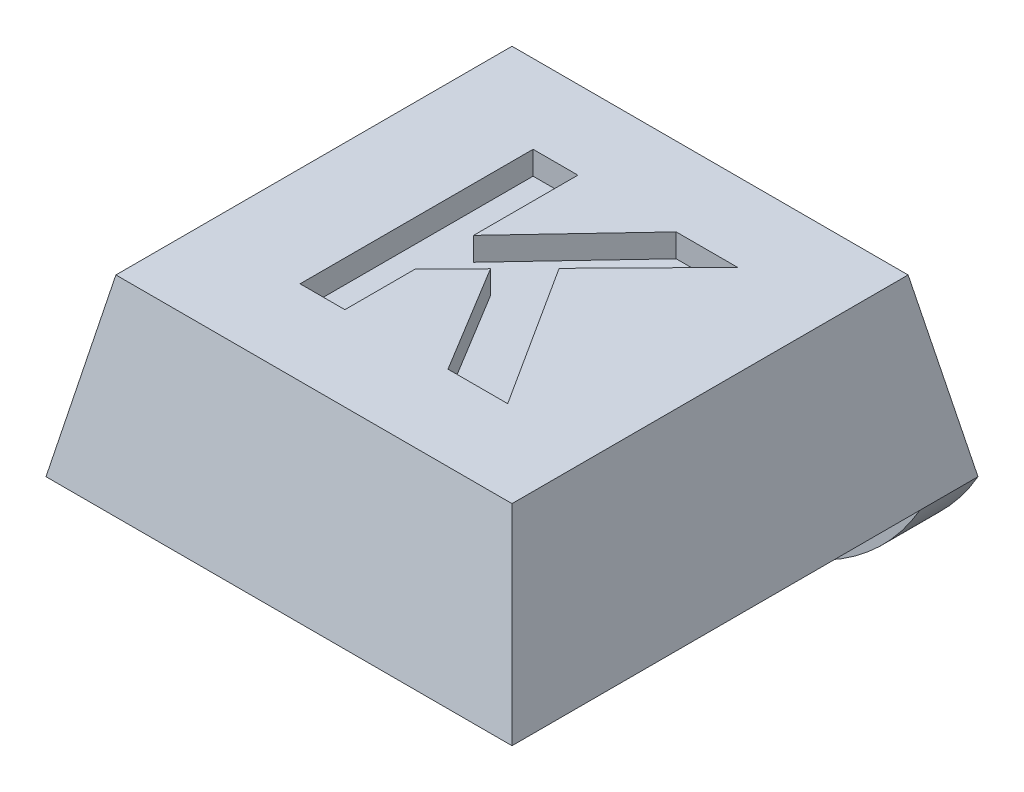
SolidWorks part; units mm, degrees
ref_plane "Front Plane" through (0, 0, 0) normal (0, 0, 1) x (1, 0, 0)
ref_plane "Top Plane" through (0, 0, 0) normal (0, 1, 0) x (1, 0, 0)
ref_plane "Right Plane" through (0, 0, 0) normal (1, 0, 0) x (0, 0, -1)
sketch "Sketch1" plane through (0, 0, 0) normal (0, 1, 0) x (1, 0, 0)
  line L1 (0, 0) -> (8, 0)
  line L2 (0, 0) -> (0, 8)
  line L3 (0, 8) -> (8, 8)
  line L4 (8, 0) -> (8, 8)
  dimension "D1" = 8
  dimension "D2" = 8
extrude "Boss-Extrude1" add sketch "Sketch1" along normal blind 3
sketch "Sketch2" plane through (0, 0, 0) normal (0, 0, 1) x (1, 0, 0)
  line L0 (0, 0) -> (0.6, 3)
  line L1 (0, 3) -> (8, 3) construction
  line L2 (0.6, 3) -> (0, 3)
  line L3 (0, 3) -> (0, 0)
  line L4 (8, 0) -> (7.4, 3)
  line L5 (7.4, 3) -> (8, 3)
  line L6 (8, 3) -> (8, 0)
  dimension "D1" = 0.6
  dimension "D2" = 0.6
extrude "Cut-Extrude1" cut sketch "Sketch2" against normal through all both and the other way through all
sketch "Sketch3" plane through (0, 0, 0) normal (1, 0, 0) x (0, 0, -1)
  line L0 (0, 0) -> (0.6, 3)
  line L1 (8, 3) -> (0, 3) construction
  line L2 (0.6, 3) -> (0, 3)
  line L3 (0, 3) -> (0, 0)
  line L4 (8, 3) -> (7.4, 3)
  line L5 (7.4, 3) -> (8, 0)
  line L6 (8, 3) -> (8, 0)
  dimension "D1" = 0.6
  dimension "D2" = 0.6
extrude "Cut-Extrude2" cut sketch "Sketch3" along normal blind 11
sketch "Sketch4" plane through (0, 0, 0) normal (0, -1, 0) x (1, 0, 0)
  line L0 (8, 0) -> (8, -8) construction
  line L3 (0, 0) -> (8, 0) construction
  circle A0 centre (4, -3.75) radius 1.75
  dimension "D1" = 3.5
  dimension "D2" = 4
  dimension "D3" = 3.75
extrude "Cut-Extrude3" cut sketch "Sketch4" against normal blind 0.4
sketch "Sketch5" plane through (0, 0, 0) normal (0, -1, 0) x (1, 0, 0)
  line L0 (8, 0) -> (8, -8) construction
  line L1 (0, -8) -> (8, -8)
  line L2 (0, -8) -> (0, -7)
  line L3 (0, -7) -> (8, -7)
  line L4 (8, -8) -> (8, -7)
  dimension "D1" = 1
extrude "Boss-Extrude2" add sketch "Sketch5" along normal blind 2
fillet "Fillet1" radius 4 2 edges at (8, -2, -7.5) (0, -2, -7.5)
sketch "Sketch6" plane through (0, 3, 0) normal (0, 1, 0) x (1, 0, 0)
  text T0 "K" font "Arial" height 4
extrude "Cut-Extrude4" cut sketch "Sketch6" against normal blind 0.4
